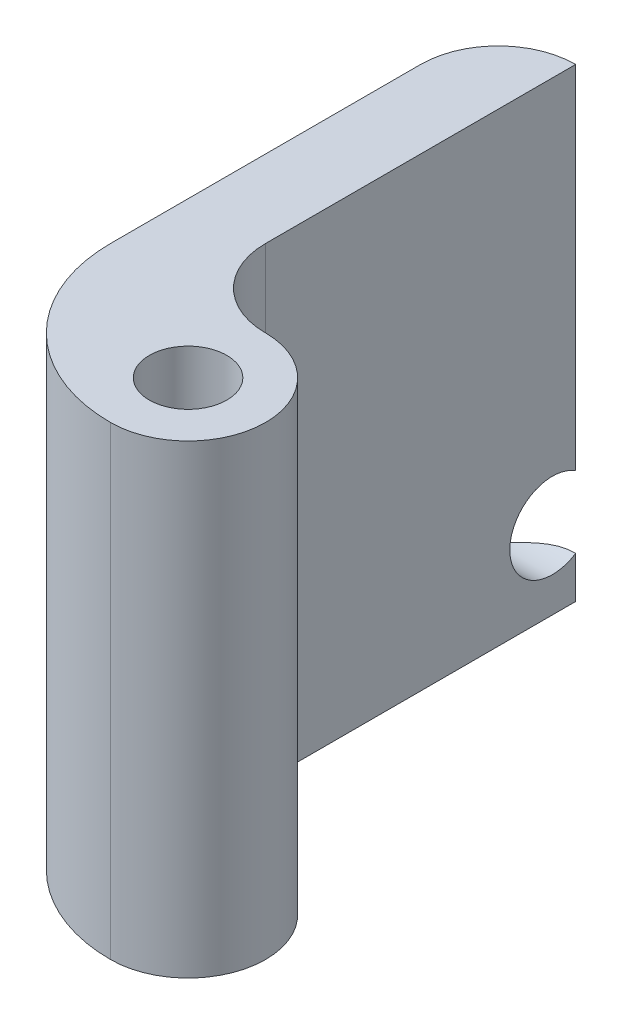
SolidWorks part; units mm, degrees
ref_plane "Front Plane" through (0, 0, 0) normal (0, 0, 1) x (1, 0, 0)
ref_plane "Top Plane" through (0, 0, 0) normal (0, 1, 0) x (1, 0, 0)
ref_plane "Right Plane" through (0, 0, 0) normal (1, 0, 0) x (0, 0, -1)
sketch "Sketch1" plane through (0, 0, 0) normal (0, 1, 0) x (1, 0, 0)
  line L0 (-5, 30) -> (-5, 10)
  line L4 (-10, 5) -> (-10, 30)
  line L5 (-10, 30) -> (-5, 30)
  arc A0 (0, -5) -> (-10, 5) centre (0, 5) cw
  arc A1 (0, 5) -> (-5, 10) centre (0, 10) cw
  arc A2 (0, -5) -> (0, 5) centre (0, 0) ccw
  circle A3 centre (0, 0) radius 2.5
  point P11 (0, 0)
  dimension "D1" = 10
  dimension "D5" = 5
  dimension "D3" = 5
  dimension "D7" = 5
  dimension "D2" = 25
  dimension "D6" = 5
extrude "Boss-Extrude1" add sketch "Sketch1" along normal blind 30
fillet "Fillet1" radius 5 1 edges at (-10, 15, -30)
extrude "Cut-Extrude1" cut sketch "Sketch2" against normal blind 124
sketch "Sketch2" plane through (5, -405, -405) normal (1, 0, 0) x (0, 0, -1)
  circle A27 centre (-380, 145.5) radius 3
  circle A28 centre (-380, 127.5) radius 3
  circle A29 centre (-380, 17) radius 3.35
  circle A30 centre (-17, 17) radius 3.35
  circle A31 centre (-17, 145.5) radius 3
  circle A32 centre (-17, 127.5) radius 3
  circle A33 centre (-113.25, 317.5) radius 3
  circle A34 centre (-113.25, 331.5) radius 3
  circle A35 centre (-151.75, 317.5) radius 3
  circle A36 centre (-151.75, 331.5) radius 3
  circle A37 centre (-293.25, 317.5) radius 3
  circle A38 centre (-293.25, 331.5) radius 3
  circle A39 centre (-331.75, 317.5) radius 3
  circle A40 centre (-331.75, 331.5) radius 3
  circle A41 centre (-17, 336) radius 3
  circle A42 centre (-17, 351) radius 3
  circle A43 centre (-17, 480) radius 3.35
  circle A44 centre (-109.5, 480) radius 3
  circle A45 centre (-127.5, 480) radius 3
  circle A46 centre (-271.5, 480) radius 3
  circle A47 centre (-289.5, 480) radius 3
  circle A48 centre (-380, 480) radius 3.35
  circle A49 centre (-351.5, 402.5) radius 2.75
  circle A50 centre (-382.5, 353.25) radius 3
  circle A51 centre (-382.5, 368.25) radius 3
  circle A52 centre (-376.5, 410) radius 2.75
  circle A53 centre (-376.5, 395) radius 2.75
  circle A54 centre (-51.5, 323) radius 3.35
  circle A55 centre (-51.5, 17) radius 3.35
  point P0 (-51.5, 17)
  point P61 (-51.5, 323)
  point P62 (-347.5, 17)
